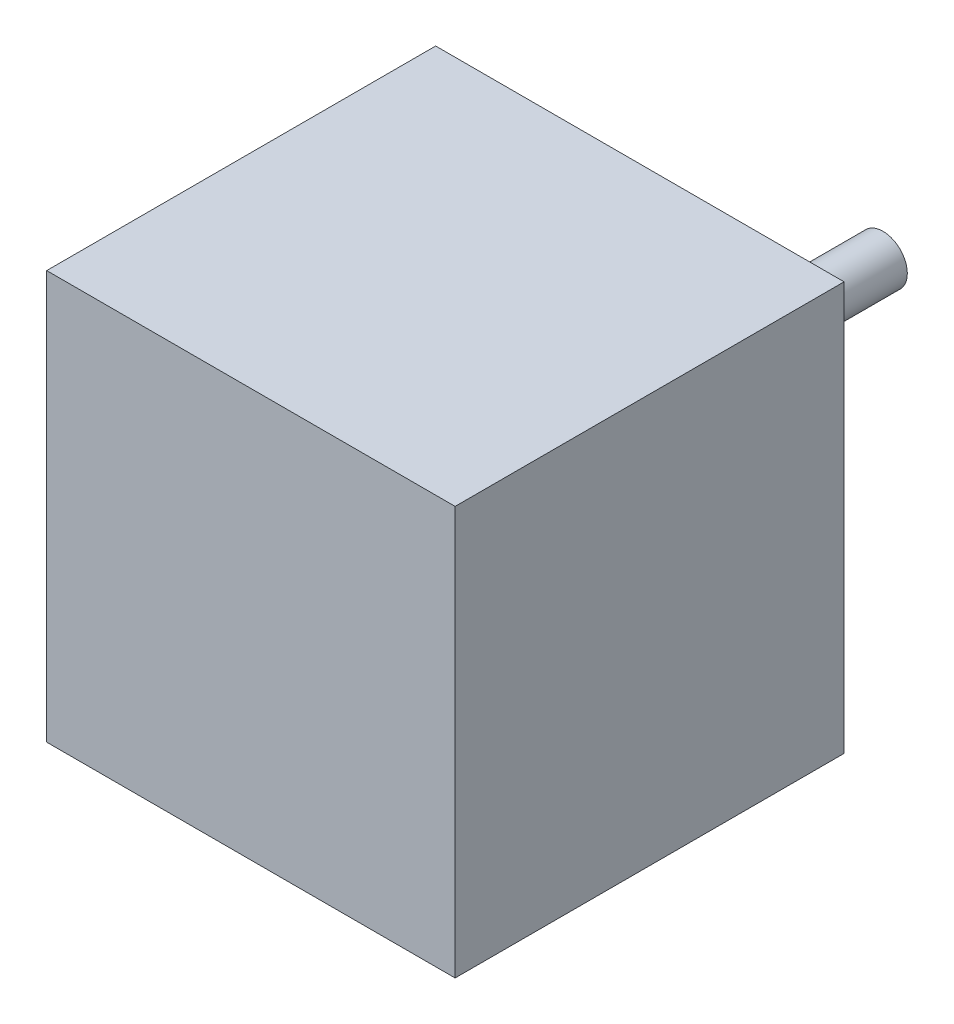
SolidWorks part; units mm, degrees
ref_plane "前视基准面" through (0, 0, 0) normal (0, 0, 1) x (1, 0, 0)
ref_plane "上视基准面" through (0, 0, 0) normal (0, 1, 0) x (1, 0, 0)
ref_plane "右视基准面" through (0, 0, 0) normal (1, 0, 0) x (0, 0, -1)
sketch "草图1" plane through (0, 0, 0) normal (0, 0, 1) x (1, 0, 0)
  line L1 (-21, -21) -> (21, -21)
  line L2 (-21, -21) -> (-21, 21)
  line L3 (-21, 21) -> (21, 21)
  line L4 (21, -21) -> (21, 21)
  line L5 (-21, -21) -> (21, 21) construction
  line L6 (-21, 21) -> (21, -21) construction
  circle A0 centre (0, 0) radius 11.5
  circle A1 centre (0, 0) radius 2.5
  point P0 (0, 0)
  dimension "D3" = 23
  dimension "D4" = 5
  dimension "D1" = 42
  dimension "D2" = 42
extrude "凸台-拉伸1" add sketch "草图1" along normal blind 40 contours L1 L4 L3 L2 A0 | A0 A1 | A1 region at (-20.406, 0, 0) region at (-11.1747, 0, 0) region at (0, 0, 0)
extrude "凸台-拉伸2" add sketch "草图1<3>" against normal blind 2 contours A0 A1 | A1 region at (-11.1747, 0, 0) region at (0, 0, 0)
sketch "草图1<3>" plane through (0, 0, 0) normal (0, 0, 1) x (1, 0, 0) same geometry as "草图1"
extrude "凸台-拉伸3" add sketch "草图1<4>" against normal blind 25 contours A1 region at (0, 0, 0)
sketch "草图1<4>" plane through (0, 0, 0) normal (0, 0, 1) x (1, 0, 0) same geometry as "草图1"
